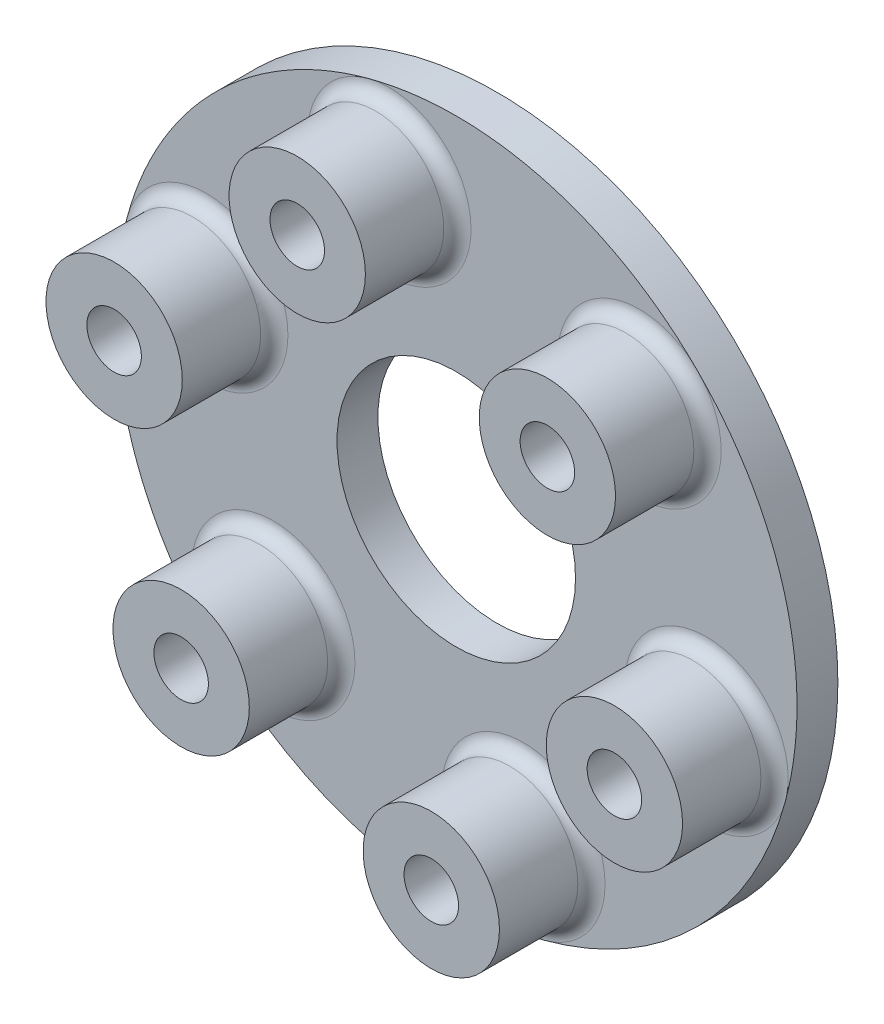
SolidWorks part; units mm, degrees
ref_plane "Front Plane" through (0, 0, 0) normal (0, 0, 1) x (1, 0, 0)
ref_plane "Top Plane" through (0, 0, 0) normal (0, 1, 0) x (1, 0, 0)
ref_plane "Right Plane" through (0, 0, 0) normal (1, 0, 0) x (0, 0, -1)
sketch "Sketch1" plane through (0, 0, 0) normal (0, 0, 1) x (1, 0, 0)
  circle A8 centre (0, 0) radius 25
  circle A9 centre (0, 0) radius 8.75
  dimension "D1" = 50
  dimension "D2" = 17.5
extrude "Boss-Extrude1" add sketch "Sketch1" along normal blind 3
sketch "Sketch2" plane through (0, 0, 3) normal (0, 0, 1) x (1, 0, 0)
  circle A1 centre (-4.9176, 18.3526) radius 5
  circle A2 centre (-18.3526, 4.9176) radius 5
  circle A3 centre (-13.435, -13.435) radius 5
  circle A4 centre (4.9176, -18.3526) radius 5
  circle A5 centre (18.3526, -4.9176) radius 5
  circle A6 centre (13.435, 13.435) radius 5
  circle A7 centre (-4.9176, 18.3526) radius 2
  circle A8 centre (-18.3526, 4.9176) radius 2
  circle A9 centre (-13.435, -13.435) radius 2
  circle A10 centre (4.9176, -18.3526) radius 2
  circle A11 centre (18.3526, -4.9176) radius 2
  circle A12 centre (13.435, 13.435) radius 2
  dimension "D2" = 10
  dimension "D3" = 10
  dimension "D4" = 10
  dimension "D5" = 10
  dimension "D6" = 10
  dimension "D7" = 10
  dimension "D8" = 4
  dimension "D9" = 4
  dimension "D10" = 4
  dimension "D11" = 4
  dimension "D12" = 4
  dimension "D13" = 4
  dimension "D14" = 19
  dimension "D15" = 19
  dimension "D16" = 19
  dimension "D17" = 19
  dimension "D18" = 19
  dimension "D19" = 19
extrude "Boss-Extrude2" add sketch "Sketch2" along normal blind 6.75
sketch "Sketch5" plane through (0, 0, 3) normal (0, 0, 1) x (1, 0, 0)
  circle A0 centre (-18.3526, 4.9176) radius 2
  circle A1 centre (-13.435, -13.435) radius 2
  circle A2 centre (4.9176, -18.3526) radius 2
  circle A3 centre (18.3526, -4.9176) radius 2
  circle A4 centre (13.435, 13.435) radius 2
  circle A5 centre (-4.9176, 18.3526) radius 2
extrude "Cut-Extrude1" cut sketch "Sketch5" against normal blind 6.75
fillet "Fillet4" radius 1 1 edges at (-8.435, -13.435, 3) type face fillet first side face at (-8.435, -13.435, 9.75) second side face at (18.435, 13.435, 3)
fillet "Fillet5" radius 1 1 edges at (-13.3526, 4.9176, 3) type face fillet first side face at (-13.3526, 4.9176, 9.75) second side face at (18.435, 13.435, 3)
fillet "Fillet6" radius 1 1 edges at (0.0824, 18.3526, 3) type face fillet first side face at (0.0824, 18.3526, 9.75) second side face at (18.435, 13.435, 3)
fillet "Fillet7" radius 1 1 edges at (18.435, 13.435, 3) type face fillet first side face at (18.435, 13.435, 9.75) second side face at (18.435, 13.435, 3)
fillet "Fillet8" radius 1 1 edges at (23.3526, -4.9176, 3) type face fillet first side face at (23.3526, -4.9176, 9.75) second side face at (23.3526, -4.9176, 3)
fillet "Fillet9" radius 1 1 edges at (9.9176, -18.3526, 3) type face fillet first side face at (9.9176, -18.3526, 9.75) second side face at (9.9176, -18.3526, 3)
